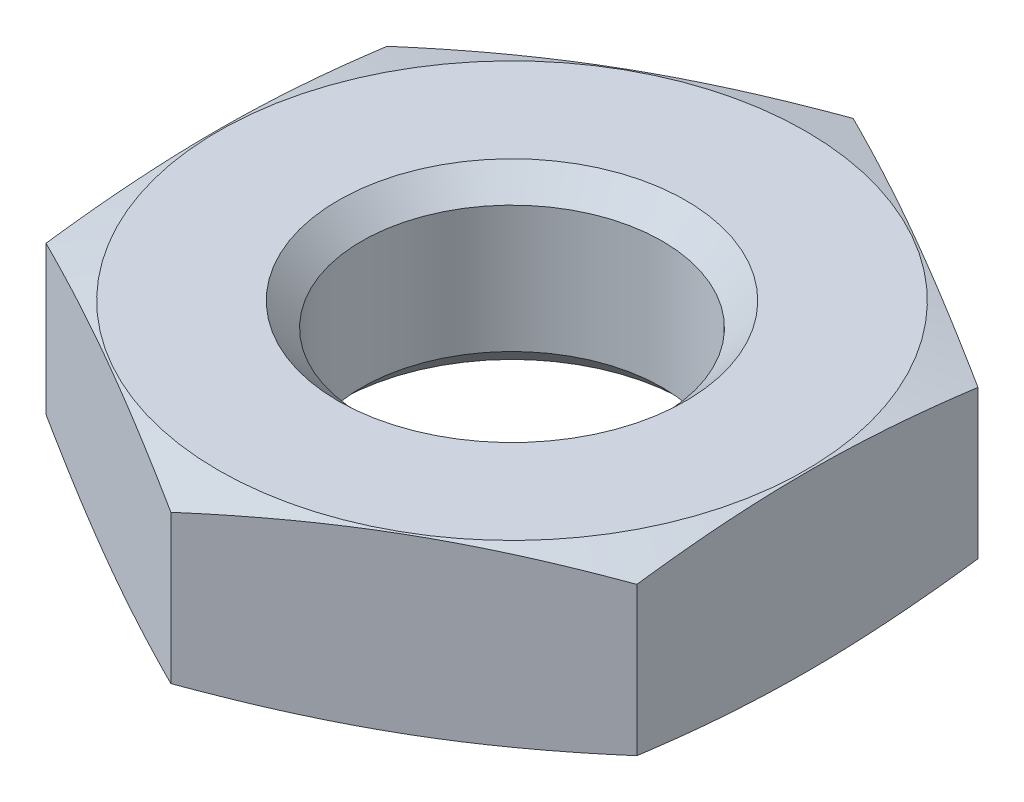
SolidWorks part; units mm, degrees
ref_plane "Ebene vorne" through (0, 0, 0) normal (0, 0, 1) x (1, 0, 0)
ref_plane "Ebene oben" through (0, 0, 0) normal (0, 1, 0) x (1, 0, 0)
ref_plane "Ebene rechts" through (0, 0, 0) normal (1, 0, 0) x (0, 0, -1)
sketch "Skizze1" plane through (0, 0, 0) normal (0, 0, 1) x (1, 0, 0)
  line L0 (0, 0) -> (8.45, 0)
  line L1 (8.45, 0) -> (17.7801, -2.5)
  line L2 (17.7801, -2.5) -> (8.45, -5)
  line L3 (8.45, -5) -> (0, -5)
  line L4 (0, -5) -> (0, 0)
  line L5 (0, -5) -> (0, 0) construction
revolve "Rotation1" add sketch "Skizze1" angle 360 about L5
sketch "Skizze2" plane through (0, 0, 0) normal (0, 1, 0) x (1, 0, 0)
  line L0 (-34, 34) -> (-34, -34)
  line L1 (-34, -34) -> (34, -34)
  line L2 (34, -34) -> (34, 34)
  line L3 (34, 34) -> (-34, 34)
  line L4 (-8.5, -4.9075) -> (0, -9.815)
  line L5 (0, -9.815) -> (8.5, -4.9075)
  line L6 (8.5, -4.9075) -> (8.5, 4.9075)
  line L7 (8.5, 4.9075) -> (0, 9.815)
  line L8 (0, 9.815) -> (-8.5, 4.9075)
  line L9 (-8.5, 4.9075) -> (-8.5, -4.9075)
extrude "Schnitt-Linear austragen1" cut sketch "Skizze2" along normal blind 6 and the other way blind 6
sketch "Skizze3" plane through (0, 0, 0) normal (0, 0, 1) x (1, 0, 0)
  line L0 (0, 0) -> (5, 0)
  line L1 (5, 0) -> (4.3235, -0.6765)
  line L2 (4.3235, -0.6765) -> (4.3235, -4.3235)
  line L3 (4.3235, -4.3235) -> (5, -5)
  line L4 (5, -5) -> (0, -5)
  line L5 (0, -5) -> (0, 0)
  line L6 (0, -5) -> (0, 0) construction
revolve "Schnitt-Rotation1" cut sketch "Skizze3" angle 360 about L6 reverse direction yes
cosmetic thread "Gewindedarstellung1" parameters "D1"=5, "D2"=10
ref_plane "Ebene1" through (0, -2.5, 0) normal (0, 1, 0) x (1, 0, 0)
ref_plane "2CYL XY" through (0, -2.5, 0) normal (0, 1, 0) x (1, 0, 0)
ref_plane "2CYL XZ" through (0, 0, 0) normal (0, 0, 1) x (1, 0, 0)
ref_plane "2CYL YZ" through (0, 0, 0) normal (1, 0, 0) x (0, 0, -1)
ref_axis "2CYL X" through (-80.9, -2.5, 0) along (1, 0, 0)
ref_axis "2CYL Y" through (0, -2.5, 50) along (0, 0, -1)
ref_axis "2CYL Z" through (0, 50, 0) along (0, -1, 0)
sketch3d "2CYL"
  point P0 (0, -2.5, 0)
ref_plane "din439b_punkt XY" through (0, 0, 0) normal (0, 1, 0) x (1, 0, 0)
ref_plane "din439b_punkt XZ" through (0, 0, 0) normal (0, 0, 1) x (1, 0, 0)
ref_plane "din439b_punkt YZ" through (0, 0, 0) normal (1, 0, 0) x (0, 0, -1)
ref_axis "din439b_punkt X" through (-80.9, 0, 0) along (1, 0, 0)
ref_axis "din439b_punkt Y" through (0, 0, 50) along (0, 0, -1)
ref_axis "din439b_punkt Z" through (0, 50, 0) along (0, -1, 0)
sketch3d "din439b_punkt"
  point P0 (0, 0, 0)
